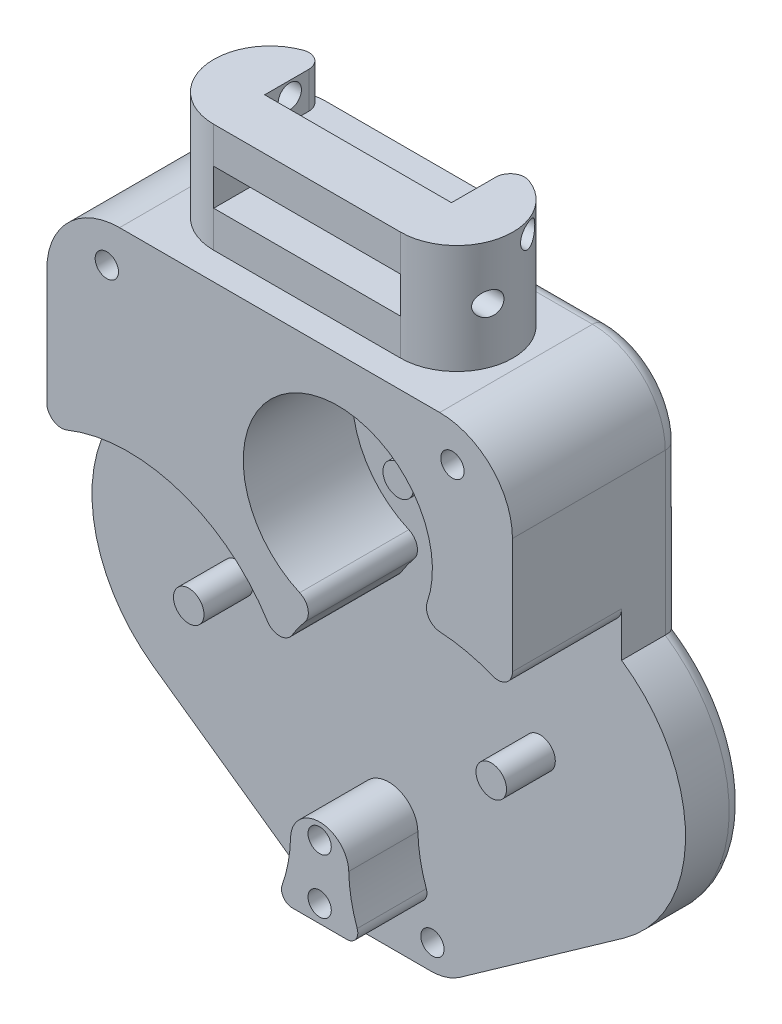
SolidWorks part; units mm, degrees
ref_plane "Alzado" through (0, 0, 0) normal (0, 0, 1) x (1, 0, 0)
ref_plane "Planta" through (0, 0, 0) normal (0, 1, 0) x (1, 0, 0)
ref_plane "Vista lateral" through (0, 0, 0) normal (1, 0, 0) x (0, 0, -1)
sketch "Croquis1" plane through (0, 0, 0) normal (0, 0, 1) x (1, 0, 0)
  line L0 (-9.1775, 40) -> (9.1775, 40)
  line L2 (32.3363, -22.7922) -> (8, -40)
  line L3 (8, -40) -> (-8, -40)
  line L4 (0, 40) -> (0, -40) construction
  line L5 (-32.3363, -22.7922) -> (-8, -40)
  line L7 (24.4498, 13.2001) -> (24.4498, 27.2001)
  line L8 (-24.4498, 13.2001) -> (-24.4498, 27.2001)
  arc A1 (24.4498, 13.2001) -> (32.3363, -22.7922) centre (20.7895, -6.4621) cw
  arc A3 (-24.4498, 13.2001) -> (-32.3363, -22.7922) centre (-20.7895, -6.4621) ccw
  arc A4 (24.4498, 27.2001) -> (9.1775, 40) centre (11.4498, 27.2001) ccw
  arc A5 (-24.4498, 27.2001) -> (-9.1775, 40) centre (-11.4498, 27.2001) cw
  point P7 (0, 0)
  dimension "D4" = 14
  dimension "D5" = 13
  dimension "D2" = 20
  dimension "D1" = 9.1775
  dimension "D3" = 80
  dimension "D6" = 8
extrude "Saliente-Extruir1" add sketch "Croquis1" along normal blind 20 contours A3 L5 L3 L2 A1 L7 A4 L0 A5 L8
sketch "Croquis2" plane through (0, 0, 20) normal (0, 0, 1) x (1, 0, 0)
  line L0 (-20.7895, -6.4621) -> (-0.0045, -6.4621) construction
  line L1 (20.7895, -6.4621) -> (0.0045, -6.4621) construction
  line L2 (0, -40) -> (0, 40) construction
  line L3 (8, -40) -> (-8, -40) construction
  line L4 (-9.1775, 40) -> (9.1775, 40) construction
  arc A0 (0, 2.143) -> (0, -15.0672) centre (-20.7895, -6.4621) ccw
  arc A1 (0, -15.0672) -> (18.9832, 15.9653) centre (20.7895, -6.4621) ccw
  circle A2 centre (-20.7895, -6.4621) radius 20.785 construction
  circle A3 centre (20.7895, -6.4621) radius 20.785 construction
  arc A6 (18.9832, 15.9653) -> (5.6059, 10.1424) centre (8, 22.9201) ccw
  circle A7 centre (8, 22.9201) radius 11.26 construction
  arc A8 (5.6059, 10.1424) -> (0, 2.143) centre (20.7895, -6.4621) ccw
  dimension "D1" = 45
  dimension "D2" = 41.57
  dimension "D3" = 26
  dimension "D4" = 22.52
  dimension "D5" = 8
extrude "Cortar-Extruir1" cut sketch "Croquis2" against normal blind 12 contours A0 A1 A6 A8
sketch "Croquis3" plane through (0, 0, 20) normal (0, 0, 1) x (1, 0, 0)
  line L3 (-23.9199, -28.7432) -> (-8, -40)
  line L4 (-8, -40) -> (8, -40)
  line L5 (8, -40) -> (23.9199, -28.7432)
  line L6 (-23.9199, -28.7432) -> (-8, -40)
  line L7 (-8, -40) -> (8, -40)
  line L8 (8, -40) -> (23.9199, -28.7432)
  arc A2 (0, -15.0672) -> (23.9199, -28.7432) centre (20.7895, -6.4621) ccw
  arc A3 (-23.9199, -28.7432) -> (0, -15.0672) centre (-20.7895, -6.4621) ccw
  arc A4 (0, -15.0672) -> (23.9199, -28.7432) centre (20.7895, -6.4621) ccw
  arc A5 (-23.9199, -28.7432) -> (0, -15.0672) centre (-20.7895, -6.4621) ccw
  dimension "D1" = 0
extrude "Cortar-Extruir2" cut sketch "Croquis3" against normal up to surface (12 mm away) up to face at (1.4203, -0.7032, 8)
fillet "Redondeo1" radius 2 2 edges at (5.6059, 10.1424, 14) (0, 2.143, 14)
sketch "Croquis4" plane through (0, 0, 8) normal (0, 0, 1) x (1, 0, 0)
  circle A0 centre (-20.7895, -6.4621) radius 2.1
  circle A1 centre (20.7895, -6.4621) radius 2.1
  circle A2 centre (8, 22.9201) radius 2.1
  dimension "D1" = 4.2
extrude "Saliente-Extruir2" add sketch "Croquis4" along normal blind 6.7
fillet "Redondeo2" radius 7 2 edges at (8, -40, 4) (-8, -40, 4)
sketch "Croquis5" plane through (0, 0, 8) normal (0, 0, 1) x (1, 0, 0)
  line L0 (0, -40) -> (0, 0) construction
  line L1 (5.7752, -40) -> (-5.7752, -40) construction
  circle A0 centre (6, -36.5) radius 3.5 construction
  circle A1 centre (6, -36.5) radius 1.6
  circle A2 centre (-6, -36.5) radius 1.6
  circle A3 centre (-6, -36.5) radius 3.5 construction
  dimension "D1" = 7
  dimension "D2" = 3.2
  dimension "D3" = 6
extrude "Cortar-Extruir3" cut sketch "Croquis5" against normal through all
sketch "Croquis6" plane through (0, 0, 8) normal (0, 0, 1) x (1, 0, 0)
  line L0 (-6, -32.5) -> (6, -32.5)
  line L2 (0, -40) -> (0, 40) construction
  line L3 (5.7752, -40) -> (-5.7752, -40) construction
  line L4 (0, -32.5) -> (0, -20) construction
  arc A1 (6, -32.5) -> (3.9987, -24.28) centre (23.9921, -23.7658) cw
  arc A2 (3.9987, -24.28) -> (-3.9987, -24.28) centre (0, -24.3828) ccw
  arc A3 (-6, -32.5) -> (-3.9987, -24.28) centre (-23.9921, -23.7658) ccw
  point P3 (0, -32.5)
  dimension "D2" = 20
  dimension "D1" = 7.5
  dimension "D3" = 8.22
  dimension "D4" = 12
  dimension "D6" = 4
extrude "Saliente-Extruir3" add sketch "Croquis6" along normal blind 9.5 contours A1 A2 A3 L0
fillet "Redondeo3" radius 1.5 2 edges at (6, -32.5, 12.75) (-6, -32.5, 12.75)
sketch "Croquis7" plane through (0, 0, 17.5) normal (0, 0, 1) x (1, 0, 0)
  line L0 (0, -32.5) -> (0, -20.3828) construction
  line L1 (-3.7457, -32.5) -> (3.7457, -32.5) construction
  line L2 (0, -20.3828) -> (0, -40) construction
  line L3 (0, -26.2214) -> (-3.6539, -26.2214) construction
  line L4 (0, -26.4414) -> (-3.6539, -26.4414) construction
  line L5 (0, -31.7014) -> (-2.3243, -31.7014) construction
  line L6 (0, -20.9614) -> (-1.6, -20.9614) construction
  arc A0 (3.9987, -24.28) -> (-3.9987, -24.28) centre (0, -24.3828) ccw construction
  circle A1 centre (0, -22.5614) radius 1.6
  circle A2 centre (0, -30.1014) radius 1.6
  circle A3 centre (0, -22.5614) radius 3.66 construction
  circle A4 centre (0, -30.1014) radius 3.66 construction
  point P11 (0, -26.4414)
  dimension "D1" = 3.2
  dimension "D4" = 7.32
  dimension "D2" = 3.88
  dimension "D3" = 3.66
extrude "Cortar-Extruir4" cut sketch "Croquis7" against normal through all
sketch "Croquis8" plane through (0, 0, 20) normal (0, 0, 1) x (1, 0, 0)
  line L3 (24.4498, 15.7382) -> (24.4498, 27.2001)
  line L4 (9.1775, 40) -> (-9.1775, 40)
  line L5 (-24.4498, 27.2001) -> (-24.4498, 15.7382)
  line L6 (24.4498, 15.7382) -> (24.4498, 27.2001)
  line L7 (9.1775, 40) -> (-9.1775, 40)
  line L8 (-24.4498, 27.2001) -> (-24.4498, 15.7382)
  arc A11 (3.4843, 7.9178) -> (1.6971, 5.443) centre (20.7895, -6.4621) ccw
  arc A12 (3.4843, 7.9178) -> (2.7533, 11.0259) centre (1.9461, 9.196) ccw
  arc A13 (18.9832, 15.9653) -> (2.7533, 11.0259) centre (8, 22.9201) ccw
  arc A14 (3.4843, 7.9178) -> (2.7533, 11.0259) centre (1.9461, 9.196) ccw
  arc A15 (24.4498, 15.7382) -> (18.9832, 15.9653) centre (20.7895, -6.4621) ccw
  arc A17 (24.4498, 27.2001) -> (9.1775, 40) centre (11.4498, 27.2001) ccw
  arc A18 (-9.1775, 40) -> (-24.4498, 27.2001) centre (-11.4498, 27.2001) ccw
  arc A20 (-1.6971, 5.443) -> (-24.4498, 15.7382) centre (-20.7895, -6.4621) ccw
  arc A22 (3.4843, 7.9178) -> (1.6971, 5.443) centre (20.7895, -6.4621) ccw
  arc A24 (18.9832, 15.9653) -> (2.7533, 11.0259) centre (8, 22.9201) ccw
  arc A26 (24.4498, 15.7382) -> (18.9832, 15.9653) centre (20.7895, -6.4621) ccw
  arc A28 (24.4498, 27.2001) -> (9.1775, 40) centre (11.4498, 27.2001) ccw
  arc A29 (-9.1775, 40) -> (-24.4498, 27.2001) centre (-11.4498, 27.2001) ccw
  arc A31 (-1.6971, 5.443) -> (-24.4498, 15.7382) centre (-20.7895, -6.4621) ccw
  arc A36 (-1.6971, 5.443) -> (1.6971, 5.443) centre (0, 6.5013) ccw
  arc A37 (-1.6971, 5.443) -> (1.6971, 5.443) centre (0, 6.5013) ccw
  dimension "D1" = 0
extrude "Saliente-Extruir4" add sketch "Croquis8" along normal blind 3
sketch "Croquis9" plane through (0, 0, 0) normal (0, 0, -1) x (-1, 0, 0)
  line L1 (-22, 42.1007) -> (22, 42.1007)
  line L4 (9.1775, 40) -> (-9.1775, 40) construction
  line L7 (9.1775, 40) -> (-9.1775, 40)
  line L9 (-24.4498, 27.2001) -> (-24.4498, 13.2001)
  line L10 (-32, 32.1007) -> (-32, 10.1007)
  line L11 (32, 32.1007) -> (32, 10.1007)
  line L12 (24.4498, 13.2001) -> (24.4498, 27.2001) construction
  line L13 (24.4498, 13.2001) -> (24.4498, 27.2001)
  arc A2 (24.4498, 27.2001) -> (9.1775, 40) centre (11.4498, 27.2001) ccw construction
  arc A3 (-9.1775, 40) -> (-24.4498, 27.2001) centre (-11.4498, 27.2001) ccw construction
  arc A5 (24.4498, 27.2001) -> (9.1775, 40) centre (11.4498, 27.2001) ccw
  arc A6 (-9.1775, 40) -> (-24.4498, 27.2001) centre (-11.4498, 27.2001) ccw
  arc A8 (22, 42.1007) -> (32, 32.1007) centre (22, 32.1007) cw
  arc A9 (-32, 32.1007) -> (-22, 42.1007) centre (-22, 32.1007) cw
  arc A10 (-24.4498, 13.2001) -> (-32.3363, -22.7922) centre (-20.7895, -6.4621) ccw construction
  arc A11 (32.3363, -22.7922) -> (24.4498, 13.2001) centre (20.7895, -6.4621) ccw construction
  arc A12 (32, 10.1007) -> (24.4498, 13.2001) centre (20.7895, -6.4621) ccw
  arc A13 (-24.4498, 13.2001) -> (-32, 10.1007) centre (-20.7895, -6.4621) ccw
  point P6 (0, 42.1007)
  point P17 (32, 45.0907)
  point P23 (-32, 45.0907)
  dimension "D3" = 10
  dimension "D1" = 32
  dimension "D2" = 64
extrude "Saliente-Extruir6" add sketch "Croquis9" against normal up to surface (23 mm away) up to face at (1.8969, 22.1404, 23)
sketch "Croquis10" plane through (0, 0, 23) normal (0, 0, 1) x (1, 0, 0)
  line L0 (32, 32.1007) -> (32, 10.1007) construction
  line L1 (24.4498, 13.2001) -> (24.4498, 15.7382) construction
  line L2 (32, 13.0462) -> (32, 10.1007)
  line L3 (24.4498, 13.2001) -> (24.4498, 15.7382)
  arc A0 (0, -15.0672) -> (18.9832, 15.9653) centre (20.7895, -6.4621) ccw construction
  arc A1 (32, 10.1007) -> (24.4498, 13.2001) centre (20.7895, -6.4621) ccw construction
  arc A2 (32, 13.0462) -> (24.4498, 15.7382) centre (20.7895, -6.4621) ccw
  arc A3 (32, 10.1007) -> (24.4498, 13.2001) centre (20.7895, -6.4621) ccw
extrude "Cortar-Extruir5" cut sketch "Croquis10" against normal up to surface (15 mm away) up to face at (0, -28.5797, 8)
mirror "Simetría1" about plane through (0, 0, 0) normal (1, 0, 0) of "Cortar-Extruir5"
fillet "Redondeo4" radius 2 15 edges at (-32, 21.1007, 0) (-29.0711, 39.1717, 0) (0, 42.1007, 0) (29.0711, 39.1717, 0) (-40.7884, -6.2576, 0) (-21.0764, -30.7538, 0) (-7.8955, -39.6712, 0) (0, -40, 0) (7.8955, -39.6712, 0) (21.0764, -30.7538, 0) (32, 21.1007, 0) (40.7884, -6.2576, 0) (18.9832, 15.9653, 15.5) (32, 13.0462, 15.5) (-32, 13.0462, 15.5)
sketch "Croquis11" plane through (0, 0, 0) normal (0, 0, -1) x (-1, 0, 0)
  line L1 (2.0554, -26.1214) -> (4.1107, -22.5614)
  line L2 (4.1107, -22.5614) -> (2.0554, -19.0014)
  line L3 (2.0554, -19.0014) -> (-2.0554, -19.0014)
  line L4 (-2.0554, -19.0014) -> (-4.1107, -22.5614)
  line L5 (-4.1107, -22.5614) -> (-2.0554, -26.1214)
  line L6 (-2.0554, -26.1214) -> (2.0554, -26.1214)
  line L7 (4.1107, -30.1014) -> (2.0554, -26.5414)
  line L8 (2.0554, -26.5414) -> (-2.0554, -26.5414)
  line L9 (-2.0554, -26.5414) -> (-4.1107, -30.1014)
  line L10 (-4.1107, -30.1014) -> (-2.0554, -33.6614)
  line L11 (-2.0554, -33.6614) -> (2.0554, -33.6614)
  line L12 (2.0554, -33.6614) -> (4.1107, -30.1014)
  line L13 (-3.9446, -32.94) -> (-8.0554, -32.94)
  line L14 (-8.0554, -32.94) -> (-10.1107, -36.5)
  line L15 (-10.1107, -36.5) -> (-8.0554, -40.06)
  line L16 (-8.0554, -40.06) -> (-3.9446, -40.06)
  line L17 (-3.9446, -40.06) -> (-1.8893, -36.5)
  line L18 (-1.8893, -36.5) -> (-3.9446, -32.94)
  line L19 (8.0554, -32.94) -> (3.9446, -32.94)
  line L20 (3.9446, -32.94) -> (1.8893, -36.5)
  line L21 (1.8893, -36.5) -> (3.9446, -40.06)
  line L22 (3.9446, -40.06) -> (8.0554, -40.06)
  line L23 (8.0554, -40.06) -> (10.1107, -36.5)
  line L24 (10.1107, -36.5) -> (8.0554, -32.94)
  circle A0 centre (0, -22.5614) radius 3.56 construction
  circle A1 centre (0, -30.1014) radius 3.56 construction
  circle A2 centre (-6, -36.5) radius 3.56 construction
  circle A3 centre (6, -36.5) radius 3.56 construction
  dimension "D1" = 7.12
extrude "Cortar-Extruir6" cut sketch "Croquis11" against normal blind 3.32
sketch "Croquis12" plane through (0, 0, 0) normal (0, 0, -1) x (-1, 0, 0)
  line L0 (0, 0) -> (0, 33.42) construction
  line L1 (0, 33.42) -> (0, 40.1) construction
  circle A0 centre (23.75, 36.76) radius 1.6
  circle A1 centre (-23.75, 36.76) radius 1.6
  point P6 (0, 36.76)
  dimension "D3" = 3.2
  dimension "D1" = 33.42
  dimension "D2" = 6.68
  dimension "D4" = 23.75
extrude "Cortar-Extruir7" cut sketch "Croquis12" against normal through all
sketch "Croquis13" plane through (0, 0, 0) normal (0, 0, -1) x (-1, 0, 0)
  line L1 (-19.6393, 36.76) -> (-21.6946, 40.32)
  line L2 (-21.6946, 40.32) -> (-25.8054, 40.32)
  line L3 (-25.8054, 40.32) -> (-27.8607, 36.76)
  line L4 (-27.8607, 36.76) -> (-25.8054, 33.2)
  line L5 (-25.8054, 33.2) -> (-21.6946, 33.2)
  line L6 (-21.6946, 33.2) -> (-19.6393, 36.76)
  line L7 (25.8054, 33.2) -> (27.8607, 36.76)
  line L8 (27.8607, 36.76) -> (25.8054, 40.32)
  line L9 (25.8054, 40.32) -> (21.6946, 40.32)
  line L10 (21.6946, 40.32) -> (19.6393, 36.76)
  line L11 (19.6393, 36.76) -> (21.6946, 33.2)
  line L12 (21.6946, 33.2) -> (25.8054, 33.2)
  circle A0 centre (-23.75, 36.76) radius 3.56 construction
  circle A1 centre (23.75, 36.76) radius 3.56 construction
  dimension "D1" = 7.12
extrude "Cortar-Extruir8" cut sketch "Croquis13" against normal blind 3.32
sketch "Croquis14" plane through (0, 42.1007, 0) normal (0, 1, 0) x (1, 0, 0)
  line L1 (0, 0) -> (0, -23) construction
  line L2 (-22, -23) -> (22, -23) construction
  line L3 (-12.84, -11.5) -> (12.84, -11.5) construction
  line L4 (-12.84, -3.78) -> (12.84, -3.78)
  line L5 (-12.84, -19.22) -> (12.84, -19.22)
  arc A2 (-12.84, -3.78) -> (-12.84, -19.22) centre (-12.84, -11.5) ccw
  arc A3 (12.84, -19.22) -> (12.84, -3.78) centre (12.84, -11.5) ccw
  point P2 (20.56, -11.5)
  point P3 (-20.56, -11.5)
  point P10 (0, -11.5)
  point P15 (0, -11.5)
  dimension "D1" = 41.12
  dimension "D2" = 7.72
extrude "Saliente-Extruir7" add sketch "Croquis14" along normal blind 15
sketch "Croquis16" plane through (0, 57.1007, 0) normal (0, 1, 0) x (1, 0, 0)
  line L1 (-12.84, -3.78) -> (-12.84, -19.22)
  line L3 (-12.84, -19.22) -> (12.84, -19.22)
  line L8 (12.84, -19.22) -> (12.84, -3.78)
  line L9 (12.84, -3.78) -> (-12.84, -3.78)
extrude "Cortar-Extruir9" cut sketch "Croquis16" against normal blind 10
sketch "Croquis18" plane through (-12.84, 0, 0) normal (1, 0, 0) x (0, 0, -1)
  circle A0 centre (-14.24, 55.1907) radius 1.6
  circle A1 centre (-8.76, 49.7106) radius 1.6
sketch "Croquis20" plane through (-12.84, 0, 0) normal (1, 0, 0) x (0, 0, -1)
  line L5 (-3.78, 57.1007) -> (-19.22, 57.1007) construction
  line L6 (-3.78, 57.1007) -> (-3.78, 47.1007) construction
  line L8 (-19.22, 57.1007) -> (-19.22, 47.1007) construction
  circle A2 centre (-8.76, 55.1907) radius 1.6
  circle A3 centre (-14.24, 49.7107) radius 1.6
  dimension "D3" = 4.98
  dimension "D1" = 3.2
  dimension "D2" = 1.91
  dimension "D4" = 7.39
  dimension "D5" = 4.98
extrude "Cortar-Extruir10" cut sketch "Croquis20" against normal through all both and the other way through all
sketch "Croquis21" plane through (0, 0, 0) normal (1, 0, 0) x (0, 0, -1)
  line L1 (-19.22, 57.1007) -> (-19.22, 47.1007) construction
  line L11 (-19.22, 57.1007) -> (-19.22, 52.1007)
  line L13 (-19.22, 52.1007) -> (-14.22, 52.1007)
  line L14 (-10.78, 48.6607) -> (-10.78, 47.1007)
  line L15 (-3.78, 47.1007) -> (-19.22, 47.1007) construction
  line L16 (-10.78, 47.1007) -> (-3.78, 47.1007)
  line L17 (-3.78, 47.1007) -> (-3.78, 52.1007)
  line L18 (-3.78, 57.1007) -> (-3.78, 47.1007) construction
  line L19 (-3.78, 52.1007) -> (-8.78, 52.1007)
  line L20 (-12.22, 55.5407) -> (-12.22, 57.1007)
  line L21 (-3.78, 57.1007) -> (-19.22, 57.1007) construction
  line L22 (-12.22, 57.1007) -> (-19.22, 57.1007)
  arc A4 (-14.22, 52.1007) -> (-10.78, 48.6607) centre (-14.22, 48.6607) cw
  arc A5 (-12.22, 55.5407) -> (-8.78, 52.1007) centre (-8.78, 55.5407) ccw
  dimension "D1" = 7
  dimension "D2" = 5
extrude "Saliente-Extruir8" add sketch "Croquis21" along normal up to next and the other way up to next
fillet "Redondeo5" radius 2 2 edges at (-12.84, 54.6007, 3.78) (12.84, 54.6007, 3.78)
